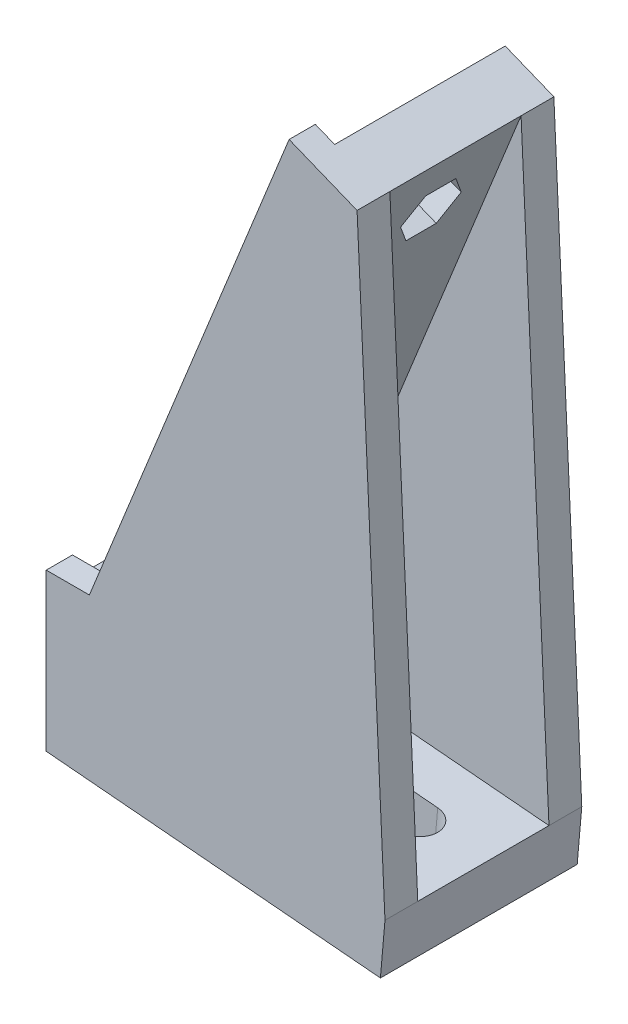
SolidWorks part; units mm, degrees
ref_plane "Front Plane" through (0, 0, 0) normal (0, 0, 1) x (1, 0, 0)
ref_plane "Top Plane" through (0, 0, 0) normal (0, 1, 0) x (1, 0, 0)
ref_plane "Right Plane" through (0, 0, 0) normal (1, 0, 0) x (0, 0, -1)
sketch "Sketch1" plane through (0, 0, 0) normal (0, 0, 1) x (1, 0, 0)
  line L0 (0, 0) -> (29.9685, 74.1747)
  line L3 (65.2738, -16.9226) -> (1.7911, -16.9226) construction
  line L4 (1.7911, -16.9226) -> (37.386, 71.1779)
  line L5 (37.386, 71.1779) -> (29.9685, 74.1747)
  line L7 (0, 0) -> (0, -3.175)
  line L8 (0, -3.175) -> (-10, -3.175)
  line L9 (0, -3.175) -> (-280, -3.175) construction
  line L10 (-10, -3.175) -> (-10, -23.9215)
  line L11 (194.4997, -41.8129) -> (-483.4753, 17.5022) construction
  line L12 (-10, -23.9215) -> (40.9417, -28.3783)
  line L13 (40.9417, -28.3783) -> (41.6389, -20.4088)
  line L15 (1.7911, -16.9226) -> (41.6389, -20.4088)
  point P4 (66.1654, -26.2884)
  point P15 (1.7911, -16.9226)
  point P18 (37.386, 71.1779)
  point P19 (-10, -3.175)
  point P20 (59.7478, -22.0541)
  dimension "D1" = 8
  dimension "D2" = 68
  dimension "D3" = 8
  dimension "D4" = 80
  dimension "D5" = 10
  dimension "D6" = 40
extrude "Boss-Extrude1" add sketch "Sketch1" along normal mid plane 30
sketch "Sketch2" plane through (-1.0772, -16.6716, 0) normal (0.0872, 0.9962, 0) x (0.9962, -0.0872, 0)
  line L0 (32.8793, 0) -> (27.8793, 0) construction
  line L1 (32.8793, -3) -> (27.8793, -3)
  line L2 (32.8793, 3) -> (27.8793, 3)
  line L4 (42.8793, -15) -> (42.8793, 15) construction
  arc A0 (32.8793, -3) -> (32.8793, 3) centre (32.8793, 0) ccw
  arc A1 (27.8793, 3) -> (27.8793, -3) centre (27.8793, 0) ccw
  point P3 (30.3793, 0)
  point P8 (34.8105, 0)
  dimension "D3" = 3
  dimension "D1" = 5
  dimension "D2" = 10
extrude "Cut-Extrude1" cut sketch "Sketch2" against normal through all
sketch "Sketch3" plane through (7.4175, -2.9969, 0) normal (0.9272, -0.3746, 0) x (0, 0, -1)
sketch "Sketch4" plane through (0, 0, 15) normal (0, 0, 1) x (1, 0, 0)
  line L0 (37.386, 71.1779) -> (41.6389, -20.4088)
  line L1 (40.9417, -28.3783) -> (41.6389, -20.4088) construction
  line L2 (41.6389, -20.4088) -> (1.7911, -16.9226) construction
  point P4 (70, 8)
  point P5 (41.6389, -20.4088)
rib "Rib1" sketch "Sketch4" sketch "Sketch4" thickness 5 extrusion direction parallel to sketch draft on no parameters "D1"=5
mirror "Mirror1" about plane through (0, 0, 0) normal (0, 0, 1) of "Rib1"
sketch "Sketch6" plane through (7.4175, -2.9969, 0) normal (0.9272, -0.3746, 0) x (0, 0, -1)
  line L0 (-10, 80) -> (10, 80) construction
  point P0 (0, 70)
  point P2 (0, 25)
  point P9 (0, 80)
  dimension "D1" = 10
  dimension "D2" = 45
hole_wizard "M4 Clearance Hole1" positions "Sketch6" profile "Sketch7" hole size "M4" standard "ANSI Metric" end condition through all
sketch "Sketch7" plane through (33.6399, 61.906, 0) normal (0, 0, 1) x (0.3746, 0.9272, 0)
  line L0 (0, 0) -> (0, 45.0582)
  line L1 (0, 45.0582) -> (2.25, 45.0582)
  line L2 (2.25, 45.0582) -> (2.25, 0.025)
  line L3 (2.25, 0.025) -> (2.275, 0)
  line L5 (2.275, 0) -> (0, 0)
  line L6 (-2.25, 0.025) -> (-2.275, 0) construction
  line L11 (0, -6.35) -> (0, 107.95) construction
  dimension "Thru Hole Dia." = 4.5
  dimension "Thru Hole Depth" = 45.0582
  dimension "Near C'Sink Dia." = 4.55
  dimension "Near C'Sink Angle" = 90
sketch "Sketch8" plane through (7.4175, -2.9969, 0) normal (0.9272, -0.3746, 0) x (0, 0, -1)
  line L1 (4.6188, 70) -> (2.3094, 74)
  line L2 (2.3094, 74) -> (-2.3094, 74)
  line L3 (-2.3094, 74) -> (-4.6188, 70)
  line L4 (-4.6188, 70) -> (-2.3094, 66)
  line L5 (-2.3094, 66) -> (2.3094, 66)
  line L6 (2.3094, 66) -> (4.6188, 70)
  line L7 (4.6188, 25) -> (2.3094, 29)
  line L8 (2.3094, 29) -> (-2.3094, 29)
  line L9 (-2.3094, 29) -> (-4.6188, 25)
  line L10 (-4.6188, 25) -> (-2.3094, 21)
  line L11 (-2.3094, 21) -> (2.3094, 21)
  line L12 (2.3094, 21) -> (4.6188, 25)
  circle A0 centre (0, 70) radius 4 construction
  circle A1 centre (0, 25) radius 4 construction
  dimension "D1" = 8
  dimension "D2" = 8
extrude "Cut-Extrude2" cut sketch "Sketch8" against normal blind 3
fillet "Fillet1" radius 10 1 edges at (1.7911, -16.9226, 0)
sketch "Sketch11" plane through (0, 0, 15) normal (0, 0, 1) x (1, 0, 0)
  line L0 (-10, -3.175) -> (-10, 0)
  line L1 (-10, 0) -> (-3.4243, 0)
  line L2 (-3.4243, 0) -> (27.0247, 75.3641)
  line L3 (27.0247, 75.3641) -> (29.9685, 74.1747)
  line L4 (29.9685, 74.1747) -> (0, 0) construction
  line L5 (-10, -3.175) -> (0, -3.175)
  line L6 (0, -3.175) -> (0, 0)
  line L7 (0, 0) -> (29.9685, 74.1747)
  dimension "D1" = 3.175
extrude "Boss-Extrude2" add sketch "Sketch11" against normal blind 4
